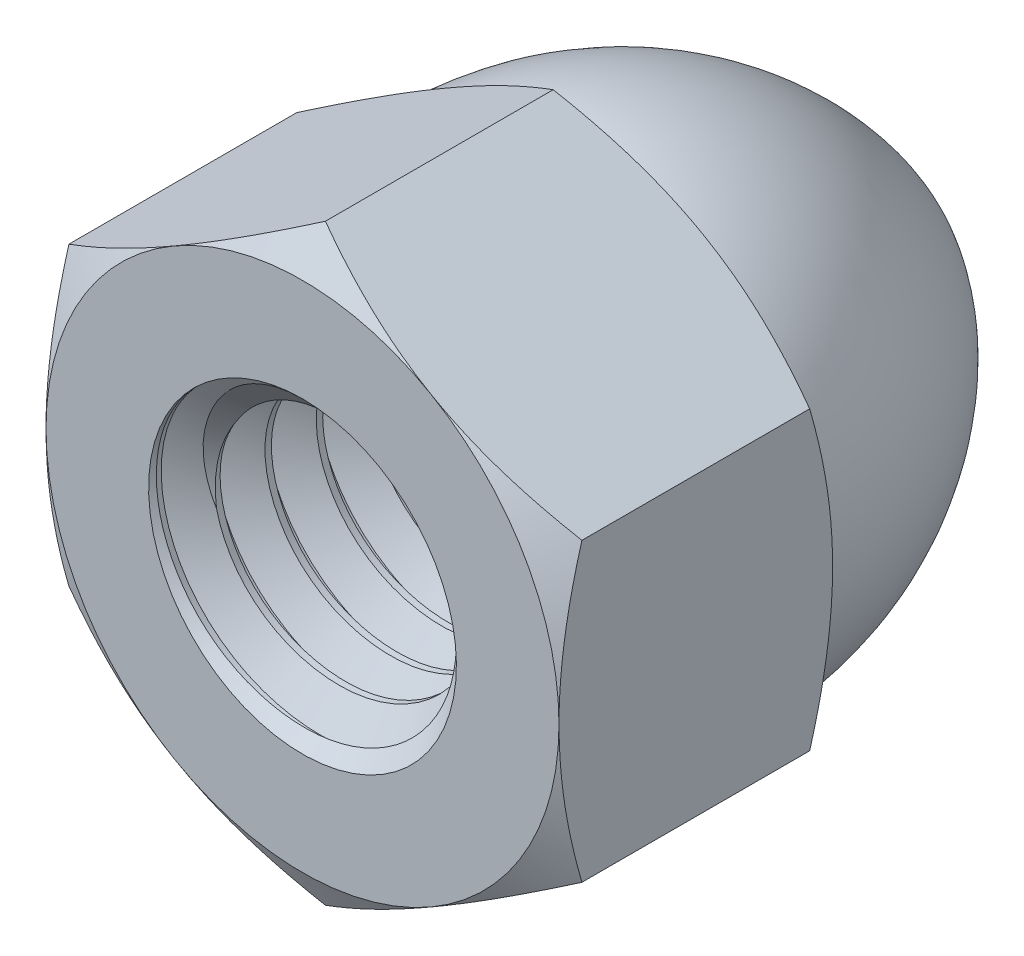
SolidWorks part; units mm, degrees
material "AISI 304"
ref_plane "Front Plane" through (0, 0, 0) normal (0, 0, 1) x (1, 0, 0)
ref_plane "Top Plane" through (0, 0, 0) normal (0, 1, 0) x (1, 0, 0)
ref_plane "Right Plane" through (0, 0, 0) normal (1, 0, 0) x (0, 0, -1)
sketch "Sketch1" plane through (0, 0, 0) normal (0, 0, 1) x (1, 0, 0)
  line L1 (0, 5.7735) -> (-5, 2.8868)
  line L2 (-5, 2.8868) -> (-5, -2.8868)
  line L3 (-5, -2.8868) -> (0, -5.7735)
  line L4 (0, -5.7735) -> (5, -2.8868)
  line L5 (5, -2.8868) -> (5, 2.8868)
  line L6 (5, 2.8868) -> (0, 5.7735)
  circle A0 centre (0, 0) radius 5 construction
  dimension "Hex" = 10
extrude "Extrude1" add sketch "Sketch1" against normal blind 5.3333
sketch "Sketch2" plane through (0, 0, 0) normal (0, 0, 1) x (1, 0, 0)
  circle A0 centre (0, 0) radius 5 construction
  circle A1 centre (0, 0) radius 5
extrude "Cut-Extrude1" cut sketch "Sketch2" against normal through all draft 60 flip side to cut
sketch "Sketch3" plane through (0, 0, -5.3333) normal (0, 0, -1) x (-1, 0, 0)
  circle A1 centre (0, 0) radius 5
  circle A2 centre (0, 0) radius 5
  dimension "D1" = 0
extrude "Cut-Extrude2" cut sketch "Sketch3" against normal through all draft 60 flip side to cut
sketch "Sketch14" plane through (0, 0, 0) normal (1, 0, 0) x (0, 0, -1)
  line L0 (5.3333, 4.95) -> (5.3333, 0)
  line L1 (5.3333, 0) -> (12, 0)
  line L2 (5.3333, 0) -> (5.3333, 4.3301) construction
  line L3 (5.3333, 5) -> (11.6149, 5) construction
  line L4 (5.3333, 4.95) -> (14.0961, 4.95) construction
  line L6 (0, 0) -> (5.3333, 0) construction
  arc A0 (5.3333, 4.95) -> (12, 0) centre (5.3333, -2.0143) cw
  dimension "D1" = 9.9
  dimension "overall length" = 12
revolve "Revolve1" add sketch "Sketch14" angle 360 about L6
sketch "Sketch4" plane through (0, 0, 0) normal (0, 0, 1) x (1, 0, 0)
  circle A0 centre (0, 0) radius 3
  dimension "Thread Dia" = 6
extrude "Cut-Extrude3" cut sketch "Sketch4" against normal blind 6
sketch "Sketch5" plane through (0, 0, 0) normal (0, 0, 1) x (1, 0, 0)
  circle A0 centre (0, 0) radius 3 construction
  circle A1 centre (0, 0) radius 3
sketch "Sketch15" plane through (0, 0, -6) normal (0, 0, 1) x (1, 0, 0)
  circle A0 centre (0, 0) radius 3 construction
  circle A1 centre (0, 0) radius 3
curve "Helix/Spiral2" pitch 1 height 8 turns 8 parameters "pitch"=1
sketch "Sketch18" plane through (0, 0, 0) normal (0, 0, 1) x (1, 0, 0)
  circle A0 centre (0, 0) radius 3 construction
  circle A1 centre (0, 0) radius 3
sketch "Sketch16" plane through (0, 0, 0) normal (1, 0, 0) x (0, 0, -1)
  line L0 (6, 3) -> (6.875, 3)
  line L1 (6.875, 3) -> (6.5, 2.3505)
  line L2 (6.5, 2.3505) -> (6.375, 2.3505)
  line L3 (6.375, 2.3505) -> (6, 3)
  line L4 (6.4375, 2.3505) -> (6.4375, 3) construction
  line L5 (6.1875, 2.6752) -> (6.6875, 2.6752) construction
  line L6 (6, 3) -> (6, -3) construction
  dimension "D1" = 60
  dimension "D2" = 0.125
  dimension "D3" = 0.5
sweep "Sweep1" add profiles "Sketch16" path "Helix/Spiral2"
sketch "Sketch17" plane through (0, 0, 0) normal (0, 0, 1) x (1, 0, 0)
  line L6 (0, 5.7735) -> (-5, 2.8868)
  line L7 (-5, 2.8868) -> (-5, -2.8868)
  line L8 (-5, -2.8868) -> (0, -5.7735)
  line L9 (0, -5.7735) -> (5, -2.8868)
  line L10 (5, -2.8868) -> (5, 2.8868)
  line L11 (5, 2.8868) -> (0, 5.7735)
  line L12 (0, 5.7735) -> (-5, 2.8868)
  line L13 (-5, 2.8868) -> (-5, -2.8868)
  line L14 (-5, -2.8868) -> (0, -5.7735)
  line L15 (0, -5.7735) -> (5, -2.8868)
  line L16 (5, -2.8868) -> (5, 2.8868)
  line L17 (5, 2.8868) -> (0, 5.7735)
  dimension "D1" = 0
extrude "Cut-Extrude8" cut sketch "Sketch17" along normal through all
extrude "Cut-Extrude9" cut sketch "Sketch18" against normal through all draft 45
sketch "Sketch20" plane through (0, 0, 0) normal (1, 0, 0) x (0, 0, -1)
  line L0 (6.3333, 3) -> (8.0654, 0)
  line L1 (6, 3) -> (6.3333, 3)
  line L2 (6, 3) -> (6, 0)
  line L3 (6, 3) -> (6.875, 3) construction
  line L4 (6, 3) -> (6, -3) construction
  line L5 (6, 0) -> (8.0654, 0)
  line L6 (0, 0) -> (-3.6507, 0) construction
  dimension "D1" = 0.3333
  dimension "D2" = 60
revolve "Cut-Revolve1" cut sketch "Sketch20" angle 360 about L6
equation "\"D2@Sketch16\" = \"pitch@Helix/Spiral2\"*.125"
equation "\"D3@Sketch16\" = \"pitch@Helix/Spiral2\"*.50"
equation "\"D1@Sketch20\" = \"pitch@Helix/Spiral2\"/3"
equation "\"D3@Helix/Spiral2\" = \"Thread Depth@Cut-Extrude3\"+2"
equation "\"Nut Height@Extrude1\" = \"overall length@Sketch14\"/2.25"
equation "\"D1@Sketch14\" = \"Hex@Sketch1\"*.99"
